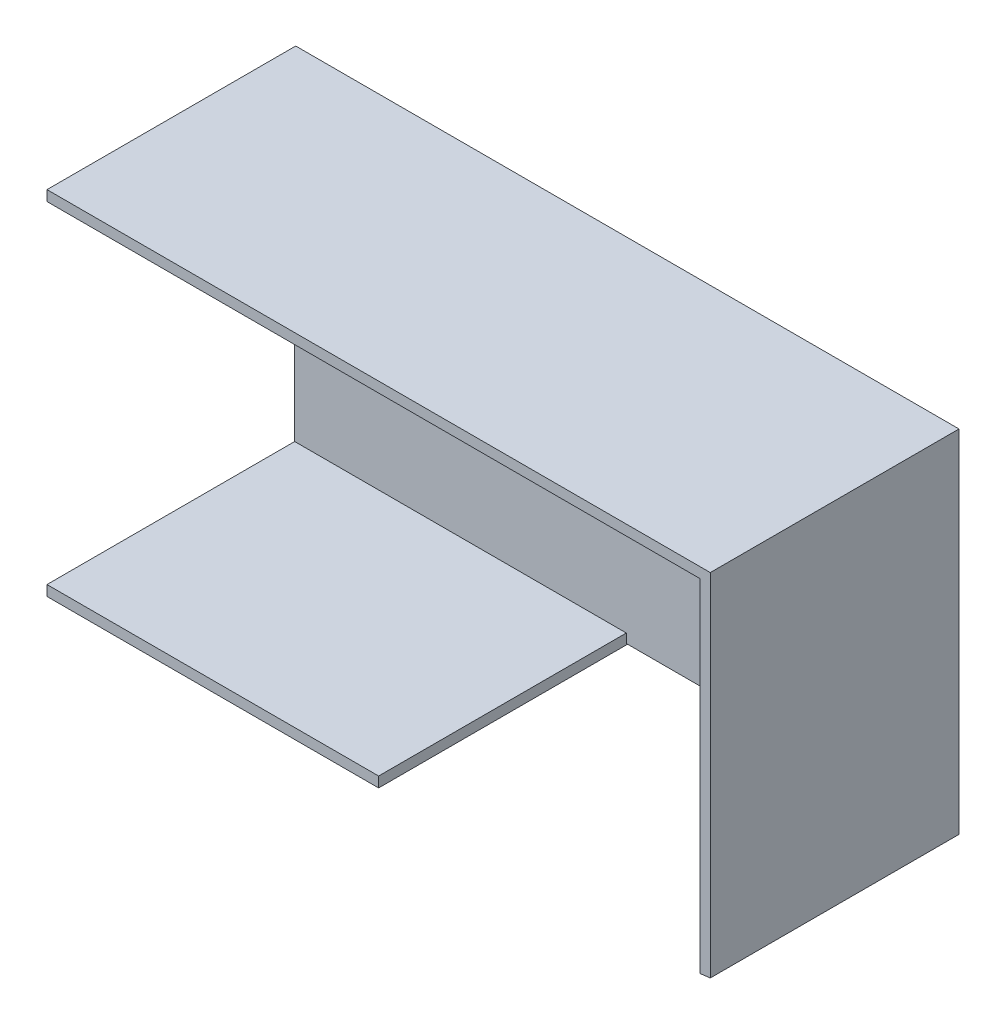
SolidWorks part; units mm, degrees
ref_plane "Front Plane" through (0, 0, 0) normal (0, 0, 1) x (1, 0, 0)
ref_plane "Top Plane" through (0, 0, 0) normal (0, 1, 0) x (1, 0, 0)
ref_plane "Right Plane" through (0, 0, 0) normal (1, 0, 0) x (0, 0, -1)
sketch "Sketch1" plane through (0, 0, 0) normal (0, 0, 1) x (1, 0, 0)
  line L0 (0, 0) -> (400.0965, 0)
  line L2 (0, 0) -> (0, 6.35)
  line L3 (0, 6.35) -> (406.4, 6.35)
  line L5 (0, -209.55) -> (203.2, -209.55)
  line L6 (0, -209.55) -> (0, -203.2)
  line L7 (0, -203.2) -> (203.2, -203.2)
  line L8 (203.2, -209.55) -> (203.2, -203.2)
  line L9 (400.0965, 0) -> (400.0965, -209.55)
  line L10 (400.0965, -209.55) -> (406.4, -208.7829)
  line L11 (406.4, -208.7829) -> (406.4, 6.35)
  line L12 (0, -203.2) -> (0, 0)
  line L13 (203.2, -209.55) -> (400.0965, -209.55)
  dimension "D1" = 406.4
  dimension "D2" = 6.35
  dimension "D3" = 6.35
  dimension "D4" = 203.2
  dimension "D5" = 0
  dimension "D6" = 6.35
  dimension "D7" = 203.2
extrude "Boss-Extrude1" add sketch "Sketch1" along normal blind 152.4 contours L10 L11 L3 L2 L0 L9 | L5 L8 L7 L6 region at (4.6019, 3.175, 0) region at (101.6, -206.375, 0)
sketch "Sketch3" plane through (0, 0, 0) normal (0, 0, -1) x (-1, 0, 0)
  line L4 (-406.4, -208.7829) -> (0, -208.7829)
  line L5 (0, -208.7829) -> (0, 6.35)
  line L6 (0, 6.35) -> (-406.4, 6.35)
  line L7 (-406.4, 6.35) -> (-406.4, -208.7829)
  dimension "D1" = 406.4
extrude "Boss-Extrude2" add sketch "Sketch3" against normal blind 0.635
